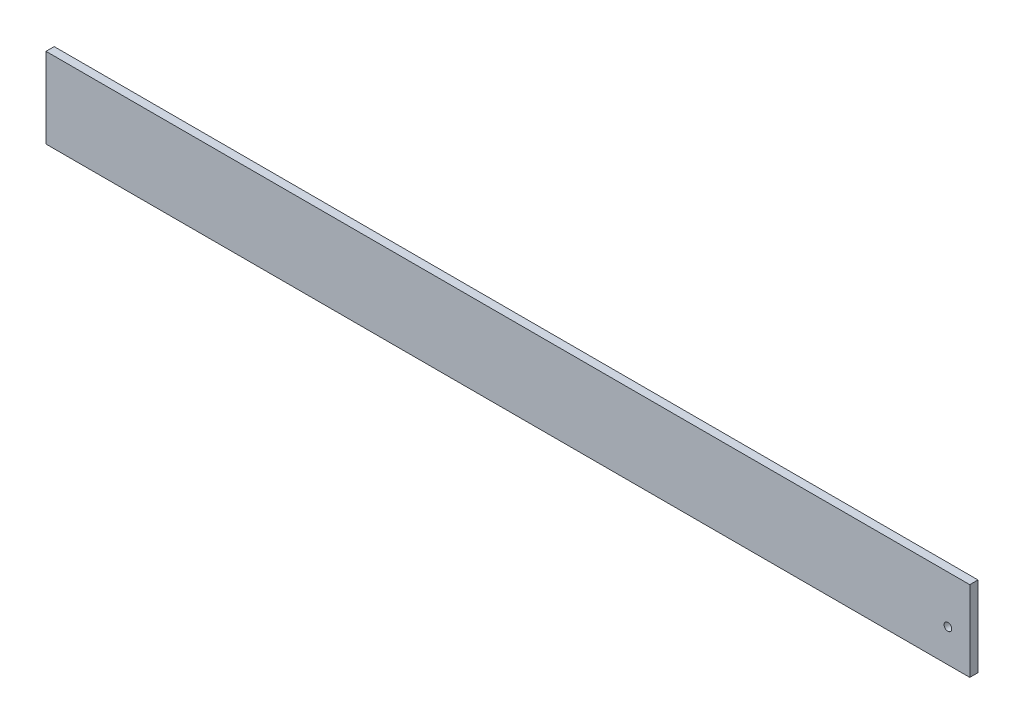
SolidWorks part; units mm, degrees
ref_plane "Front Plane" through (0, 0, 0) normal (0, 0, 1) x (1, 0, 0)
ref_plane "Top Plane" through (0, 0, 0) normal (0, 1, 0) x (1, 0, 0)
ref_plane "Right Plane" through (0, 0, 0) normal (1, 0, 0) x (0, 0, -1)
sketch "Sketch1" plane through (0, 0, 0) normal (0, 0, 1) x (1, 0, 0)
  line L1 (-253, -22) -> (253, -22)
  line L2 (-253, -22) -> (-253, 22)
  line L3 (-253, 22) -> (253, 22)
  line L4 (253, -22) -> (253, 22)
  line L5 (-253, -22) -> (253, 22) construction
  line L6 (-253, 22) -> (253, -22) construction
  circle A0 centre (241, -4) radius 2.1 construction
  circle A1 centre (241, -4) radius 2.1
  point P0 (0, 0)
  dimension "D1" = 506
  dimension "D2" = 44
extrude "Boss-Extrude1" add sketch "Sketch1" along normal blind 4.5
